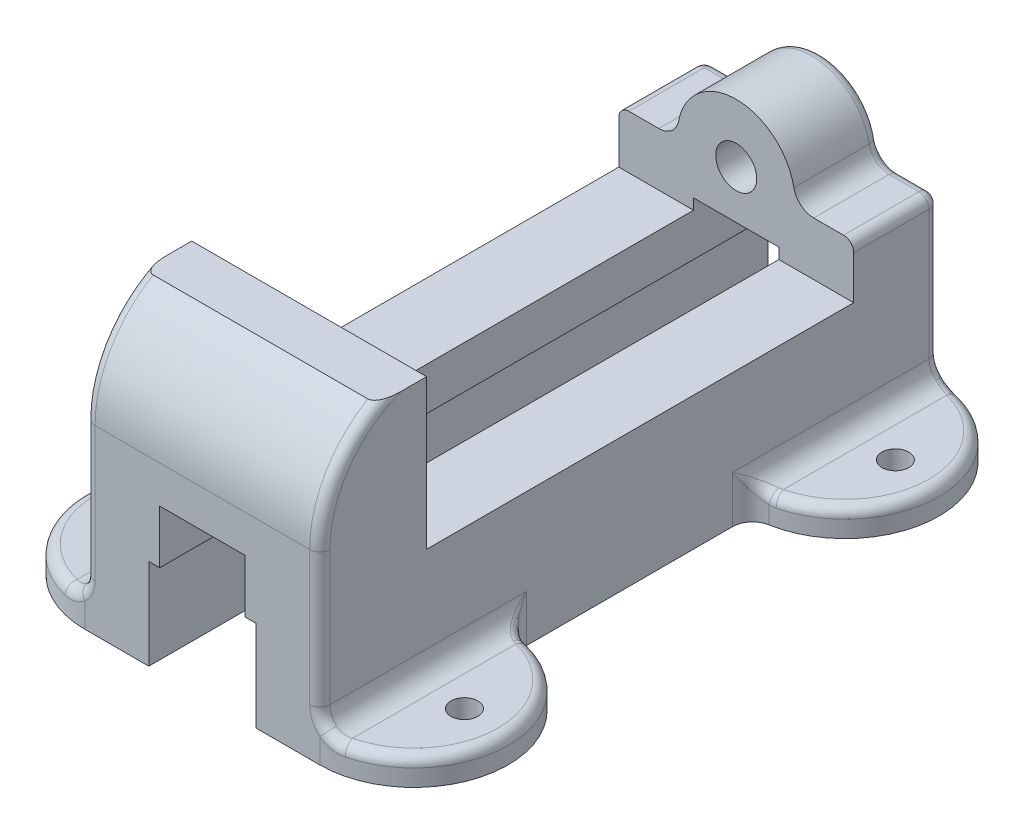
SolidWorks part; units mm, degrees
ref_plane "Alzado" through (0, 0, 0) normal (0, 0, 1) x (1, 0, 0)
ref_plane "Planta" through (0, 0, 0) normal (0, 1, 0) x (1, 0, 0)
ref_plane "Vista lateral" through (0, 0, 0) normal (1, 0, 0) x (0, 0, -1)
sketch "Croquis1" plane through (0, 0, 0) normal (0, 0, 1) x (1, 0, 0)
  line L0 (0, 0) -> (0, -58.75) construction
  line L1 (12.7, -30.18) -> (15.925, -30.18)
  line L2 (-34.925, -57.15) -> (34.925, -57.15) construction
  line L3 (-34.925, -57.15) -> (-34.925, -1.6)
  line L4 (-34.925, -1.6) -> (34.925, -1.6) construction
  line L5 (34.925, -57.15) -> (34.925, -1.6)
  line L6 (0, -1.6) -> (0, -57.15) construction
  line L7 (-34.925, -29.375) -> (34.925, -29.375) construction
  line L8 (-15.925, -30.18) -> (15.925, -30.18) construction
  line L9 (-15.925, -30.18) -> (-15.925, -57.15)
  line L10 (-15.925, -57.15) -> (15.925, -57.15) construction
  line L11 (15.925, -30.18) -> (15.925, -57.15)
  line L12 (0, -57.15) -> (0, -30.18) construction
  line L13 (-15.925, -43.665) -> (15.925, -43.665) construction
  line L14 (-12.7, -14.29) -> (12.7, -14.29)
  line L15 (-12.7, -14.29) -> (-12.7, -30.18)
  line L16 (-12.7, -30.18) -> (12.7, -30.18) construction
  line L17 (12.7, -14.29) -> (12.7, -30.18)
  line L18 (0, -30.18) -> (0, -14.29) construction
  line L19 (-12.7, -22.235) -> (12.7, -22.235) construction
  line L20 (-12.7, -30.18) -> (-15.925, -30.18)
  line L21 (-34.925, -57.15) -> (-15.925, -57.15)
  line L22 (15.925, -57.15) -> (34.925, -57.15)
  line L27 (-17.45, 0) -> (-17.45, -1.6)
  line L28 (-17.45, -1.6) -> (-34.925, -1.6)
  line L29 (17.45, 0) -> (17.45, -1.6)
  line L30 (17.45, -1.6) -> (34.925, -1.6)
  circle A0 centre (0, 0) radius 6.095
  circle A1 centre (0, 0) radius 17.45 construction
  arc A2 (-17.45, 0) -> (17.45, 0) centre (0, 0) cw
  point P7 (0, -29.375)
  point P12 (0, -43.665)
  point P16 (0, -22.235)
  point P20 (-17.45, -1.6)
  point P22 (-17.45, 0)
  dimension "D1" = 12.19
  dimension "D2" = 34.9
  dimension "D3" = 17.45
  dimension "D4" = 1.6
  dimension "D5" = 55.55
  dimension "D6" = 69.85
  dimension "D7" = 26.97
  dimension "D8" = 31.85
  dimension "D9" = 15.89
  dimension "D10" = 25.4
extrude "Saliente-Extruir2" add sketch "Croquis1" along normal blind 25.4
sketch "Croquis2" plane through (0, 0, 25.4) normal (0, 0, 1) x (1, 0, 0)
  line L0 (34.925, -57.15) -> (34.925, -1.6) construction
  line L1 (15.925, -57.15) -> (34.925, -57.15) construction
  line L2 (15.925, -30.18) -> (15.925, -57.15) construction
  line L3 (12.7, -30.18) -> (15.925, -30.18) construction
  line L4 (12.7, -14.29) -> (12.7, -30.18) construction
  line L5 (-12.7, -30.18) -> (-12.7, -14.29) construction
  line L6 (-15.925, -30.18) -> (-12.7, -30.18) construction
  line L7 (-15.925, -57.15) -> (-15.925, -30.18) construction
  line L8 (-34.925, -57.15) -> (-15.925, -57.15) construction
  line L9 (-34.925, -1.6) -> (-34.925, -57.15) construction
  line L10 (34.925, -57.15) -> (34.925, -17.48)
  line L11 (15.925, -57.15) -> (34.925, -57.15)
  line L12 (15.925, -30.18) -> (15.925, -57.15)
  line L13 (12.7, -30.18) -> (15.925, -30.18)
  line L14 (12.7, -17.48) -> (12.7, -30.18)
  line L15 (-12.7, -30.18) -> (-12.7, -17.48)
  line L16 (-15.925, -30.18) -> (-12.7, -30.18)
  line L17 (-15.925, -57.15) -> (-15.925, -30.18)
  line L18 (-34.925, -57.15) -> (-15.925, -57.15)
  line L19 (-34.925, -17.48) -> (-34.925, -57.15)
  line L20 (-34.925, -17.48) -> (-12.7, -17.48)
  line L21 (12.7, -17.48) -> (34.925, -17.48)
  dimension "D1" = 39.67
extrude "Saliente-Extruir3" add sketch "Croquis2" along normal blind 127
fillet "Redondeo1" radius 3 2 edges at (-34.925, -1.6, 12.7) (34.925, -1.6, 12.7)
fillet "Redondeo2" radius 6 2 edges at (-17.45, -1.6, 12.7) (17.45, -1.6, 12.7)
sketch "Croquis3" plane through (0, 0, 152.4) normal (0, 0, 1) x (1, 0, 0)
  line L0 (-15.925, -30.18) -> (-12.7, -30.18) construction
  line L1 (-12.7, -30.18) -> (-12.7, -17.48) construction
  line L2 (-12.7, -17.48) -> (-34.925, -17.48) construction
  line L3 (-34.925, -17.48) -> (-34.925, -57.15) construction
  line L4 (-34.925, -57.15) -> (-15.925, -57.15) construction
  line L5 (-15.925, -57.15) -> (-15.925, -30.18) construction
  line L6 (15.925, -57.15) -> (34.925, -57.15) construction
  line L7 (34.925, -57.15) -> (34.925, -17.48) construction
  line L8 (34.925, -17.48) -> (12.7, -17.48) construction
  line L9 (12.7, -17.48) -> (12.7, -30.18) construction
  line L10 (12.7, -30.18) -> (15.925, -30.18) construction
  line L11 (15.925, -30.18) -> (15.925, -57.15) construction
  line L12 (-15.925, -30.18) -> (-12.7, -30.18)
  line L13 (-12.7, -30.18) -> (-12.7, -17.48)
  line L14 (-12.7, -17.48) -> (-34.925, -17.48) construction
  line L15 (-34.925, -17.48) -> (-34.925, -57.15)
  line L16 (-34.925, -57.15) -> (-15.925, -57.15)
  line L17 (-15.925, -57.15) -> (-15.925, -30.18)
  line L18 (15.925, -57.15) -> (34.925, -57.15)
  line L19 (34.925, -57.15) -> (34.925, -17.48)
  line L20 (34.925, -17.48) -> (12.7, -17.48) construction
  line L21 (12.7, -17.48) -> (12.7, -30.18)
  line L22 (12.7, -30.18) -> (15.925, -30.18)
  line L23 (15.925, -30.18) -> (15.925, -57.15)
  line L27 (12.7, -14.29) -> (12.7, -17.48) construction
  line L28 (-34.925, -17.48) -> (34.925, -17.48) construction
  line L29 (-34.925, -17.48) -> (-34.925, 26.97)
  line L30 (-34.925, 26.97) -> (34.925, 26.97)
  line L31 (34.925, -17.48) -> (34.925, 26.97)
  line L32 (-12.7, -17.48) -> (-12.7, -14.29) construction
  line L33 (-12.7, -14.29) -> (12.7, -14.29) construction
  line L34 (12.7, -14.29) -> (12.7, -17.48)
  line L35 (-12.7, -17.48) -> (-12.7, -14.29)
  line L36 (-12.7, -14.29) -> (12.7, -14.29)
  dimension "D1" = 44.45
extrude "Saliente-Extruir4" add sketch "Croquis3" along normal blind 31.75
sketch "Croquis6" plane through (34.925, 0, 0) normal (1, 0, 0) x (0, 0, -1)
  line L4 (-184.15, -57.15) -> (-184.15, 26.97) construction
  line L5 (-184.15, 26.97) -> (-152.4, 26.97) construction
  line L6 (-184.15, -3.18) -> (-184.15, 26.97)
  line L7 (-184.15, 26.97) -> (-166.8575, 26.97)
  arc A1 (-184.15, -3.18) -> (-166.8575, 26.97) centre (-149.22, -3.18) cw
  point P3 (0, 0)
  point P8 (0, 0)
  dimension "D1" = 34.93
  dimension "D2" = 30.15
extrude "Cortar-Extruir1" cut sketch "Croquis6" against normal through all
sketch "Croquis7" plane through (0, -57.15, 0) normal (0, -1, 0) x (1, 0, 0)
  line L0 (0, 184.1867) -> (0, 0) construction
  line L1 (34.925, 92.075) -> (-34.925, 92.075) construction
  line L2 (34.925, 184.15) -> (34.925, 0) construction
  line L3 (-34.925, 184.15) -> (-34.925, 0) construction
  line L5 (34.925, 184.15) -> (34.925, 128.15)
  line L6 (34.925, 0) -> (34.925, 56)
  line L7 (-34.925, 0) -> (-34.925, 56)
  line L8 (-34.925, 184.15) -> (-34.925, 128.15)
  arc A2 (34.925, 184.15) -> (34.925, 128.15) centre (34.925, 156.15) cw
  circle A3 centre (49.925, 156.15) radius 4
  circle A4 centre (49.925, 28) radius 4
  arc A5 (34.925, 0) -> (34.925, 56) centre (34.925, 28) ccw
  arc A6 (-34.925, 0) -> (-34.925, 56) centre (-34.925, 28) cw
  circle A7 centre (-49.925, 28) radius 4
  circle A8 centre (-49.925, 156.15) radius 4
  arc A9 (-34.925, 184.15) -> (-34.925, 128.15) centre (-34.925, 156.15) ccw
  point P15 (0, 0)
  point P16 (49.925, 156.15)
  dimension "D1" = 28
  dimension "D2" = 8
  dimension "D3" = 15
  dimension "D4" = 28
extrude "Saliente-Extruir5" add sketch "Croquis7" against normal blind 8
fillet "Redondeo3" radius 6 8 edges at (34.925, -53.15, 56) (34.925, -49.15, 28) (34.925, -53.15, 128.15) (34.925, -49.15, 156.15) (-34.925, -49.15, 156.15) (-34.925, -53.15, 128.15) (-34.925, -53.15, 56) (-34.925, -49.15, 28)
fillet "Redondeo4" radius 3 29 edges at (-36.3232, -47.0001, 57.6163) (-62.925, -49.15, 28) (-37.2148, -47.8654, 0.0938) (-34.925, 14.1985, 179.52) (-34.925, -23.165, 184.15) (-36.2387, -46.8968, 184.1192) (-36.3232, -47.0001, 126.5337) (36.3232, -47.0001, 126.5337) (34.925, 14.1985, 179.52) (34.925, -23.165, 184.15) (37.2148, -47.8654, 184.0562) (-34.925, -23.875, 0) (-34.0463, -2.4787, 0) (-27.4793, -1.6, 0) (-19.2096, -0.2236, 0) (0, 17.45, 0) (19.2096, -0.2236, 0) (27.4793, -1.6, 0) (34.0463, -2.4787, 0) (34.925, -23.875, 0) (36.2387, -46.8968, 0.0308) (36.3232, -47.0001, 57.6163) (-62.925, -49.15, 156.15) (62.925, -49.15, 156.15) (62.925, -49.15, 28)
